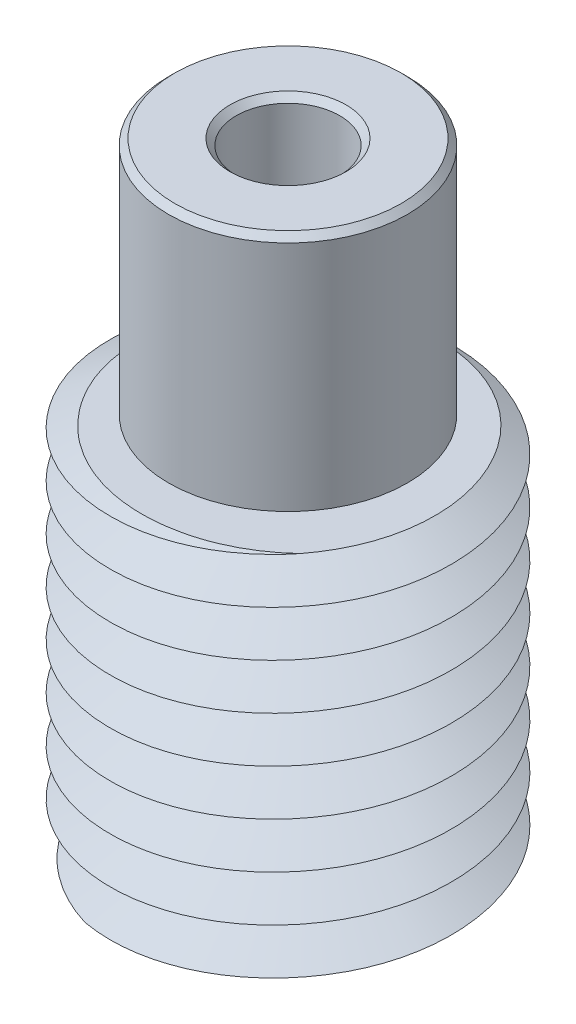
SolidWorks part; units mm, degrees
ref_plane "Front Plane" through (0, 0, 0) normal (0, 0, 1) x (1, 0, 0)
ref_plane "Top Plane" through (0, 0, 0) normal (0, 1, 0) x (1, 0, 0)
ref_plane "Right Plane" through (0, 0, 0) normal (1, 0, 0) x (0, 0, -1)
sketch "Sketch1" plane through (0, 0, 0) normal (0, 1, 0) x (1, 0, 0)
  circle A0 centre (0, 0) radius 4.7625
  dimension "D1" = 9.525
extrude "Extrude1" add sketch "Sketch1" along normal blind 9.525
chamfer "Chamfer1" distance 0.25 angle 45 1 edges at (0, 9.525, 4.7625)
sketch "Sketch2" plane through (0, 0, 0) normal (0, -1, 0) x (1, 0, 0)
  circle A0 centre (0, 0) radius 6.8707
  dimension "D1" = 13.7414
extrude "Extrude2" add sketch "Sketch2" along normal blind 14.9352
ref_point "Point1"
sketch "Sketch5" plane through (0, 9.525, 0) normal (0, 1, 0) x (1, 0, 0)
  circle A0 centre (0, 0) radius 2.0638
  dimension "D1" = 4.1275
extrude "Cut-Extrude1" cut sketch "Sketch5" against normal through all
chamfer "Chamfer2" distance 0.25 angle 45 1 edges at (0, 9.525, 2.0638)
chamfer "Chamfer3" distance 0.25 angle 45 1 edges at (0, -14.9352, 2.0638)
ref_plane "Plane1" through (0, -24.9352, 0) normal (0, -1, 0) x (1, 0, 0)
sketch "Sketch10" plane through (0, -24.9352, 0) normal (0, -1, 0) x (1, 0, 0)
  circle A0 centre (0, 0) radius 5.08
  dimension "D1" = 10.16
curve "Helix/Spiral2" pitch 1.8288 height 30 turns 16.4042
sketch "Sketch11" plane through (0, 0, 0) normal (1, 0, 0) x (0, 0, -1)
  line L0 (5.06, -1.135) -> (5.06, -3.0152) construction
  line L1 (6.8707, -1.135) -> (5.06, -2.0751)
  line L2 (6.8707, -14.9352) -> (6.8707, 0) construction
  line L3 (5.06, -2.0751) -> (6.8707, -3.0152)
  line L4 (6.8707, -3.0152) -> (6.8707, -1.135)
  spline S0 degree 3 poles (5.08, -24.9352) (5.08, -24.8973) (4.8145, -24.8206) (3.6808, -24.7062) (1.9847, -24.5917) (-0.0146, -24.4772) (-2.0117, -24.3627) (-3.7014, -24.2482) (-4.8257, -24.1337) (-5.2126, -24.0192) (-4.8033, -23.9047) (-3.6601, -23.7902) (-1.9577, -23.6757) (0.0438, -23.5612) (2.0386, -23.4467) (3.7219, -23.3321) (4.8366, -23.2176) (5.2124, -23.1031) (4.7918, -22.9886) (3.6392, -22.8741) (1.9306, -22.7596) (-0.073, -22.6451) (-2.0654, -22.5306) (-3.7423, -22.4161) (-4.8474, -22.3016) (-5.212, -22.1871) (-4.7803, -22.0726) (-3.6182, -21.9581) (-1.9034, -21.8436) (0.1022, -21.7291) (2.0922, -21.6146) (3.7626, -21.5001) (4.8581, -21.3856) (5.2114, -21.2711) (4.7686, -21.1566) (3.5972, -21.0421) (1.8762, -20.9276) (-0.1314, -20.8131) (-2.1189, -20.6986) (-3.7827, -20.5841) (-4.8686, -20.4696) (-5.2107, -20.355) (-4.7567, -20.2405) (-3.576, -20.126) (-1.8489, -20.0115) (0.1606, -19.897) (2.1456, -19.7825) (3.8028, -19.668) (4.879, -19.5535) (5.2098, -19.439) (4.7447, -19.3245) (3.5547, -19.21) (1.8216, -19.0955) (-0.1898, -18.981) (-2.1721, -18.8665) (-3.8227, -18.752) (-4.8892, -18.6375) (-5.2087, -18.523) (-4.7325, -18.4085) (-3.5333, -18.294) (-1.7942, -18.1795) (0.2189, -18.065) (2.1987, -17.9505) (3.8425, -17.836) (4.8992, -17.7215) (5.2075, -17.607) (4.7202, -17.4925) (3.5117, -17.3779) (1.7668, -17.2634) (-0.2481, -17.1489) (-2.2251, -17.0344) (-3.8621, -16.9199) (-4.9091, -16.8054) (-5.2061, -16.6909) (-4.7077, -16.5764) (-3.4901, -16.4619) (-1.7393, -16.3474) (0.2773, -16.2329) (2.2515, -16.1184) (3.8817, -16.0039) (4.9189, -15.8894) (5.2046, -15.7749) (4.6951, -15.6604) (3.4683, -15.5459) (1.7117, -15.4314) (-0.3064, -15.3169) (-2.2778, -15.2024) (-3.9011, -15.0879) (-4.9285, -14.9734) (-5.2028, -14.8589) (-4.6823, -14.7444) (-3.4465, -14.6299) (-1.6841, -14.5154) (0.3356, -14.4008) (2.304, -14.2863) (3.9204, -14.1718) (4.9379, -14.0573) (5.201, -13.9428) (4.6694, -13.8283) (3.4245, -13.7138) (1.6564, -13.5993) (-0.3647, -13.4848) (-2.3302, -13.3703) (-3.9396, -13.2558) (-4.9472, -13.1413) (-5.1989, -13.0268) (-4.6564, -12.9123) (-3.4025, -12.7978) (-1.6287, -12.6833) (0.3938, -12.5688) (2.3562, -12.4543) (3.9587, -12.3398) (4.9563, -12.2253) (5.1967, -12.1108) (4.6432, -11.9963) (3.3803, -11.8818) (1.601, -11.7673) (-0.423, -11.6528) (-2.3823, -11.5383) (-3.9776, -11.4237) (-4.9653, -11.3092) (-5.1943, -11.1947) (-4.6298, -11.0802) (-3.358, -10.9657) (-1.5731, -10.8512) (0.4521, -10.7367) (2.4082, -10.6222) (3.9964, -10.5077) (4.9741, -10.3932) (5.1918, -10.2787) (4.6163, -10.1642) (3.3356, -10.0497) (1.5453, -9.9352) (-0.4811, -9.8207) (-2.4341, -9.7062) (-4.0151, -9.5917) (-4.9827, -9.4772) (-5.1891, -9.3627) (-4.6027, -9.2482) (-3.3131, -9.1337) (-1.5174, -9.0192) (0.5102, -8.9047) (2.4598, -8.7902) (4.0337, -8.6757) (4.9912, -8.5612) (5.1863, -8.4467) (4.5889, -8.3321) (3.2905, -8.2176) (1.4894, -8.1031) (-0.5393, -7.9886) (-2.4855, -7.8741) (-4.0521, -7.7596) (-4.9996, -7.6451) (-5.1832, -7.5306) (-4.575, -7.4161) (-3.2678, -7.3016) (-1.4614, -7.1871) (0.5683, -7.0726) (2.5112, -6.9581) (4.0704, -6.8436) (5.0078, -6.7291) (5.18, -6.6146) (4.5609, -6.5001) (3.245, -6.3856) (1.4333, -6.2711) (-0.5973, -6.1566) (-2.5367, -6.0421) (-4.0886, -5.9276) (-5.0158, -5.8131) (-5.1767, -5.6986) (-4.5467, -5.5841) (-3.2221, -5.4696) (-1.4052, -5.355) (0.6263, -5.2405) (2.5622, -5.126) (4.1066, -5.0115) (5.0237, -4.897) (5.1732, -4.7825) (4.5324, -4.668) (3.1991, -4.5535) (1.3771, -4.439) (-0.6553, -4.3245) (-2.5876, -4.21) (-4.1246, -4.0955) (-5.0314, -3.981) (-5.1695, -3.8665) (-4.5179, -3.752) (-3.176, -3.6375) (-1.3489, -3.523) (0.6843, -3.4085) (2.6129, -3.294) (4.1423, -3.1795) (5.0389, -3.065) (5.1657, -2.9505) (4.5032, -2.836) (3.1528, -2.7215) (1.3207, -2.607) (-0.7132, -2.4925) (-2.6381, -2.3779) (-4.16, -2.2634) (-5.0463, -2.1489) (-5.1617, -2.0344) (-4.4885, -1.9199) (-3.1295, -1.8054) (-1.2924, -1.6909) (0.7421, -1.5764) (2.6633, -1.4619) (4.1775, -1.3474) (5.0536, -1.2329) (5.1575, -1.1184) (4.4735, -1.0039) (3.1061, -0.8894) (1.2641, -0.7749) (-0.771, -0.6604) (-2.6883, -0.5459) (-4.1949, -0.4314) (-5.0607, -0.3169) (-5.1532, -0.2024) (-4.4585, -0.0879) (-3.0826, 0.0266) (-1.2358, 0.1411) (0.7999, 0.2556) (2.7133, 0.3701) (4.2122, 0.4846) (5.0676, 0.5992) (5.1487, 0.7137) (4.4433, 0.8282) (3.059, 0.9427) (1.2074, 1.0572) (-0.8287, 1.1717) (-2.7382, 1.2862) (-4.2293, 1.4007) (-5.0743, 1.5152) (-5.1441, 1.6297) (-4.4279, 1.7442) (-3.0353, 1.8587) (-1.1789, 1.9732) (0.8575, 2.0877) (2.763, 2.2022) (4.2463, 2.3167) (5.0809, 2.4312) (5.1393, 2.5457) (4.4125, 2.6602) (3.0115, 2.7747) (1.1505, 2.8892) (-0.8863, 3.0037) (-2.7877, 3.1182) (-4.2632, 3.2327) (-5.0874, 3.3472) (-5.1343, 3.4617) (-4.3969, 3.5763) (-2.9876, 3.6908) (-1.122, 3.8053) (0.9151, 3.9198) (2.8124, 4.0343) (4.28, 4.1488) (5.0937, 4.2633) (5.1292, 4.3778) (4.3811, 4.4923) (2.9636, 4.6068) (1.0935, 4.7213) (-0.9441, 4.8358) (-2.8358, 4.9502) (-3.8124, 5.0269) (-4.1872, 5.0648) knots 0 0 0 0 0.003817 0.007634 0.01145 0.015267 0.019084 0.022901 0.026718 0.030534 0.034351 0.038168 0.041985 0.045802 0.049618 0.053435 0.057252 0.061069 0.064885 0.068702 0.072519 0.076336 0.080153 0.083969 0.087786 0.091603 0.09542 0.099237 0.103053 0.10687 0.110687 0.114504 0.118321 0.122137 0.125954 0.129771 0.133588 0.137405 0.141221 0.145038 0.148855 0.152672 0.156489 0.160305 0.164122 0.167939 0.171756 0.175573 0.179389 0.183206 0.187023 0.19084 0.194656 0.198473 0.20229 0.206107 0.209924 0.21374 0.217557 0.221374 0.225191 0.229008 0.232824 0.236641 0.240458 0.244275 0.248092 0.251908 0.255725 0.259542 0.263359 0.267176 0.270992 0.274809 0.278626 0.282443 0.28626 0.290076 0.293893 0.29771 0.301527 0.305344 0.30916 0.312977 0.316794 0.320611 0.324427 0.328244 0.332061 0.335878 0.339695 0.343511 0.347328 0.351145 0.354962 0.358779 0.362595 0.366412 0.370229 0.374046 0.377863 0.381679 0.385496 0.389313 0.39313 0.396947 0.400763 0.40458 0.408397 0.412214 0.416031 0.419847 0.423664 0.427481 0.431298 0.435115 0.438931 0.442748 0.446565 0.450382 0.454198 0.458015 0.461832 0.465649 0.469466 0.473282 0.477099 0.480916 0.484733 0.48855 0.492366 0.496183 0.5 0.503817 0.507634 0.51145 0.515267 0.519084 0.522901 0.526718 0.530534 0.534351 0.538168 0.541985 0.545802 0.549618 0.553435 0.557252 0.561069 0.564885 0.568702 0.572519 0.576336 0.580153 0.583969 0.587786 0.591603 0.59542 0.599237 0.603053 0.60687 0.610687 0.614504 0.618321 0.622137 0.625954 0.629771 0.633588 0.637405 0.641221 0.645038 0.648855 0.652672 0.656489 0.660305 0.664122 0.667939 0.671756 0.675573 0.679389 0.683206 0.687023 0.69084 0.694656 0.698473 0.70229 0.706107 0.709924 0.71374 0.717557 0.721374 0.725191 0.729008 0.732824 0.736641 0.740458 0.744275 0.748092 0.751908 0.755725 0.759542 0.763359 0.767176 0.770992 0.774809 0.778626 0.782443 0.78626 0.790076 0.793893 0.79771 0.801527 0.805344 0.80916 0.812977 0.816794 0.820611 0.824427 0.828244 0.832061 0.835878 0.839695 0.843511 0.847328 0.851145 0.854962 0.858779 0.862595 0.866412 0.870229 0.874046 0.877863 0.881679 0.885496 0.889313 0.89313 0.896947 0.900763 0.90458 0.908397 0.912214 0.916031 0.919847 0.923664 0.927481 0.931298 0.935115 0.938931 0.942748 0.946565 0.950382 0.954198 0.958015 0.961832 0.965649 0.969466 0.973282 0.977099 0.980916 0.984733 0.98855 0.992366 0.996183 1 1 1 1 construction
sweep "Cut-Sweep2" cut profiles "Sketch11" path "Helix/Spiral2"
